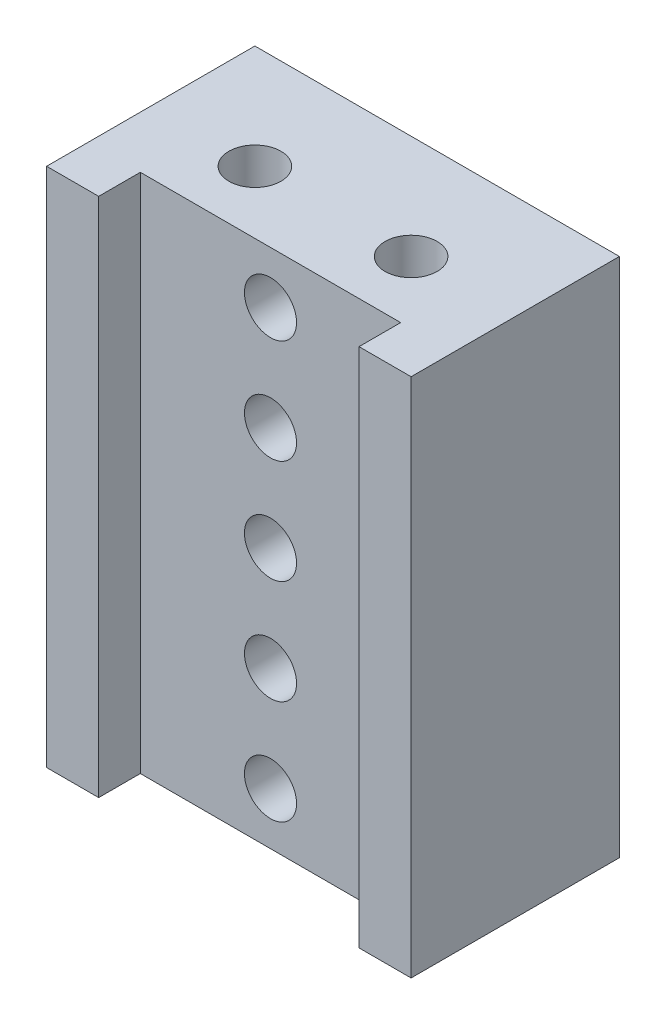
SolidWorks part; units mm, degrees
ref_plane "Front Plane" through (0, 0, 0) normal (0, 0, 1) x (1, 0, 0)
ref_plane "Top Plane" through (0, 0, 0) normal (0, 1, 0) x (1, 0, 0)
ref_plane "Right Plane" through (0, 0, 0) normal (1, 0, 0) x (0, 0, -1)
sketch "Sketch1" plane through (0, 0, 0) normal (0, 1, 0) x (1, 0, 0)
  line L1 (-17.5, 10) -> (17.5, 10)
  line L2 (-17.5, 10) -> (-17.5, -10)
  line L3 (-17.5, -10) -> (17.5, -10)
  line L4 (17.5, 10) -> (17.5, -10)
  point P4 (0, 10)
  point P6 (-17.5, 0)
  dimension "D1" = 35
  dimension "D2" = 20
extrude "Boss-Extrude1" add sketch "Sketch1" along normal blind 25 and the other way blind 25
sketch "Sketch2" plane through (0, 25, 0) normal (0, 1, 0) x (1, 0, 0)
  line L0 (0, 17.1762) -> (0, -20.8511) construction
  circle A1 centre (-7.5, 0) radius 2.5
  circle A2 centre (7.5, 0) radius 2.5
  dimension "D1" = 5
  dimension "D2" = 15
extrude "Cut-Extrude1" cut sketch "Sketch2" against normal through all both and the other way through all
sketch "Sketch3" plane through (0, 25, 0) normal (0, 1, 0) x (1, 0, 0)
  line L0 (-17.5, -10) -> (17.5, -10) construction
  line L3 (12.5, -6) -> (-12.5, -6)
  line L5 (-12.5, -6) -> (-12.5, -10)
  line L6 (-12.5, -10) -> (12.5, -10)
  line L7 (12.5, -10) -> (12.5, -6)
  point P0 (0, -10)
  point P7 (0, 0)
  point P8 (0, -10)
  dimension "D1" = 25
  dimension "D2" = 4
extrude "Cut-Extrude2" cut sketch "Sketch3" against normal through all both and the other way through all
sketch "Sketch4" plane through (0, 0, 6) normal (0, 0, 1) x (1, 0, 0)
  line L0 (0, 25) -> (0, -25) construction
  line L1 (12.5, 25) -> (-12.5, 25) construction
  line L2 (12.5, -25) -> (-12.5, -25) construction
  circle A0 centre (0, -20) radius 2.5
  circle A1 centre (0, -10) radius 2.5
  circle A2 centre (0, 0) radius 2.5
  circle A3 centre (0, 10) radius 2.5
  circle A4 centre (0, 20) radius 2.5
  point P8 (0, 0)
  point P18 (0, 4.3946)
  point P19 (0, 0)
  dimension "D2" = 5
  dimension "D3" = 10
  dimension "D1" = 5
extrude "Cut-Extrude3" cut sketch "Sketch4" against normal through all both and the other way through all
